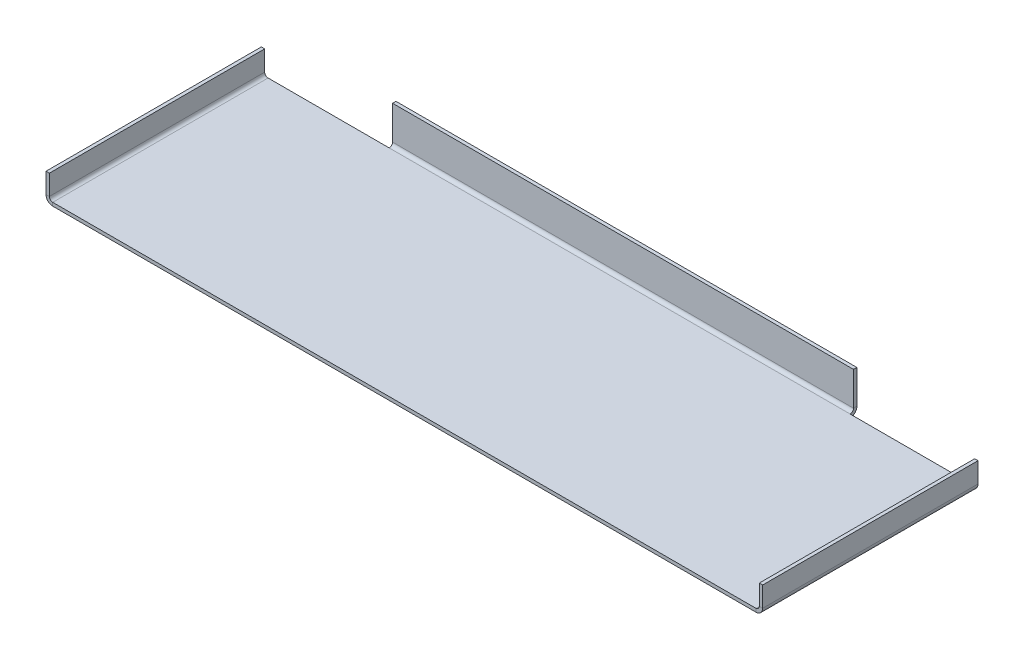
SolidWorks part; units mm, degrees
note: The reader was unsure of these and kept them because the rebuilt part matched: flange length of "Edge-Flange2", "Edge-Flange3".
material "6061-T6 (SS)"
ref_plane "X-Y Datum" through (0, 0, 0) normal (0, 0, 1) x (1, 0, 0)
ref_plane "X-Z Datum" through (0, 0, 0) normal (0, 1, 0) x (1, 0, 0)
ref_plane "Y-Z Datum" through (0, 0, 0) normal (1, 0, 0) x (0, 0, -1)
sketch "Sketch1" plane through (0, 0, 0) normal (0, 1, 0) x (1, 0, 0)
  line L1 (0, 0) -> (676.2852, 0)
  line L2 (0, 0) -> (0, 203.2)
  line L3 (0, 203.2) -> (676.2852, 203.2)
  line L4 (676.2852, 0) -> (676.2852, 203.2)
  line L9 (676.2852, 0) -> (676.2852, 203.2) construction
  dimension "D1" = 203.2
base flange "Base-Flange1" sketch "Sketch1" thickness 3.175 reverse thickness direction no parameters "D1"=3.175
edge flange "Edge-Flange2" sketch "Sketch13" flange profiles "Sketch13", "Sketch14" flange angle 90 flange length 25.4 flange position material inside bend radius 3.175 thickness 3.175 relief rectangular parameters "D6"=10, "D8"=1
sketch "Sketch13" plane through (676.2852, 0, 0) normal (1, 0, 0) x (0, 0, -1)
  line L2 (0, 0) -> (0, 22.225)
  line L3 (0, 22.225) -> (203.2, 22.225)
  line L4 (203.2, 22.225) -> (203.2, 0)
  line L7 (0, 0) -> (203.2, 0) construction
  line L8 (0, 0) -> (203.2, 0)
sketch "Sketch14" plane through (0, 0, 0) normal (-1, 0, 0) x (0, 0, 1)
  line L2 (0, 0) -> (0, 22.225)
  line L3 (0, 22.225) -> (-203.2, 22.225)
  line L4 (-203.2, 22.225) -> (-203.2, 0)
  line L5 (-203.2, 0) -> (0, 0) construction
  line L6 (-203.2, 0) -> (0, 0)
bend "EdgeBend2" bend radius 3.175 bend angle 90 parameters "D5"=2
bend "EdgeBend3" bend radius 3.175 bend angle 90 parameters "D5"=3
edge flange "Edge-Flange3" sketch "Sketch25" flange angle 90 flange length 38.1 flange position bend outside bend radius 3.175 thickness 3.175 relief rectangular parameters "D6"=10
sketch "Sketch25" plane through (0, 0, -203.2) normal (0, 0, -1) x (-1, 0, 0)
  line L2 (-555.6352, 0) -> (-555.6352, 34.925)
  line L3 (-555.6352, 34.925) -> (-120.65, 34.925)
  line L4 (-120.65, 34.925) -> (-120.65, 0)
  line L11 (-669.9352, 0) -> (-6.35, 0) construction
  line L12 (-555.6352, 0) -> (-120.65, 0)
  line L17 (-117.475, 3.175) -> (-117.475, -34.925) construction
  line L18 (-558.8102, 3.175) -> (-558.8102, -34.925) construction
  dimension "D1" = 3.175
  dimension "D2" = 3.175
bend "EdgeBend4" bend radius 3.175 bend angle 90 parameters "D5"=4
sketch "Bend-Lines1" [suppressed] plane through (0, 0, 0) normal (0, 1, 0) x (1, 0, 0)
sketch "Bounding-Box1" [suppressed] plane through (0, 0, 0) normal (0, 1, 0) x (1, 0, 0)
sheet metal parameters "Sheet-Metal1" thickness 3.175 parameters "D1"=9.525
flat pattern "Flat-Pattern1" [suppressed]
sketch "Bend-Lines2" plane through (0, 0, 0) normal (0, 1, 0) x (1, 0, 0)
sketch3d "Bounding-Box2" [suppressed]
  line L0 (673.1102, 290.83, 0) -> (0, 290.83, 0) construction
  line L1 (673.1102, 0, 0) -> (0, 0, 0) construction
  line L2 (673.1102, 290.83, 0) -> (673.1102, 0, 0) construction
  line L3 (0, 290.83, 0) -> (0, 0, 0) construction
sheet metal parameters "Sheet-Metal3" thickness 3.175 parameters "D1"=9.525
flat pattern "Flat-Pattern1"
sketch "Bend-Lines2" plane through (0, 0, 0) normal (0, 1, 0) x (1, 0, 0)
  line L2 (2.6095, 203.2) -> (2.6095, 0) construction
  line L3 (674.0465, 0) -> (674.0465, 203.2) construction
  line L4 (2.6095, 203.2) -> (2.6095, 0) construction
  line L5 (674.0465, 0) -> (674.0465, 203.2) construction
sketch3d "Bounding-Box2" [suppressed]
  line L0 (696.8369, 203.2, 0) -> (-20.1809, 203.2, 0) construction
  line L1 (696.8369, 0, 0) -> (-20.1809, 0, 0) construction
  line L2 (696.8369, 203.2, 0) -> (696.8369, 0, 0) construction
  line L3 (-20.1809, 203.2, 0) -> (-20.1809, 0, 0) construction
bend of the flat pattern "Flatten-<EdgeBend2>1"
bend of the flat pattern "Flatten-<EdgeBend3>1"
sheet metal parameters "Sheet-Metal6" thickness 3.175 parameters "D1"=9.525
flat pattern "Flat-Pattern1"
sketch "Bend-Lines2" plane through (0, 0, 0) normal (0, 1, 0) x (1, 0, 0)
  line L0 (555.6352, 206.9405) -> (120.65, 206.9405) construction
  line L1 (555.6352, 206.9405) -> (120.65, 206.9405) construction
  line L2 (2.6095, 203.2) -> (2.6095, 0) construction
  line L3 (673.6756, 0) -> (673.6756, 203.2) construction
  line L4 (2.6095, 203.2) -> (2.6095, 0) construction
  line L5 (673.6756, 0) -> (673.6756, 203.2) construction
sketch3d "Bounding-Box2" [suppressed]
  line L0 (696.4661, 242.4309, 0) -> (-20.1809, 242.4309, 0) construction
  line L1 (696.4661, 0, 0) -> (-20.1809, 0, 0) construction
  line L2 (696.4661, 242.4309, 0) -> (696.4661, 0, 0) construction
  line L3 (-20.1809, 242.4309, 0) -> (-20.1809, 0, 0) construction
bend of the flat pattern "Flatten-<EdgeBend2>1"
bend of the flat pattern "Flatten-<EdgeBend3>1"
bend of the flat pattern "Flatten-<EdgeBend4>1"
